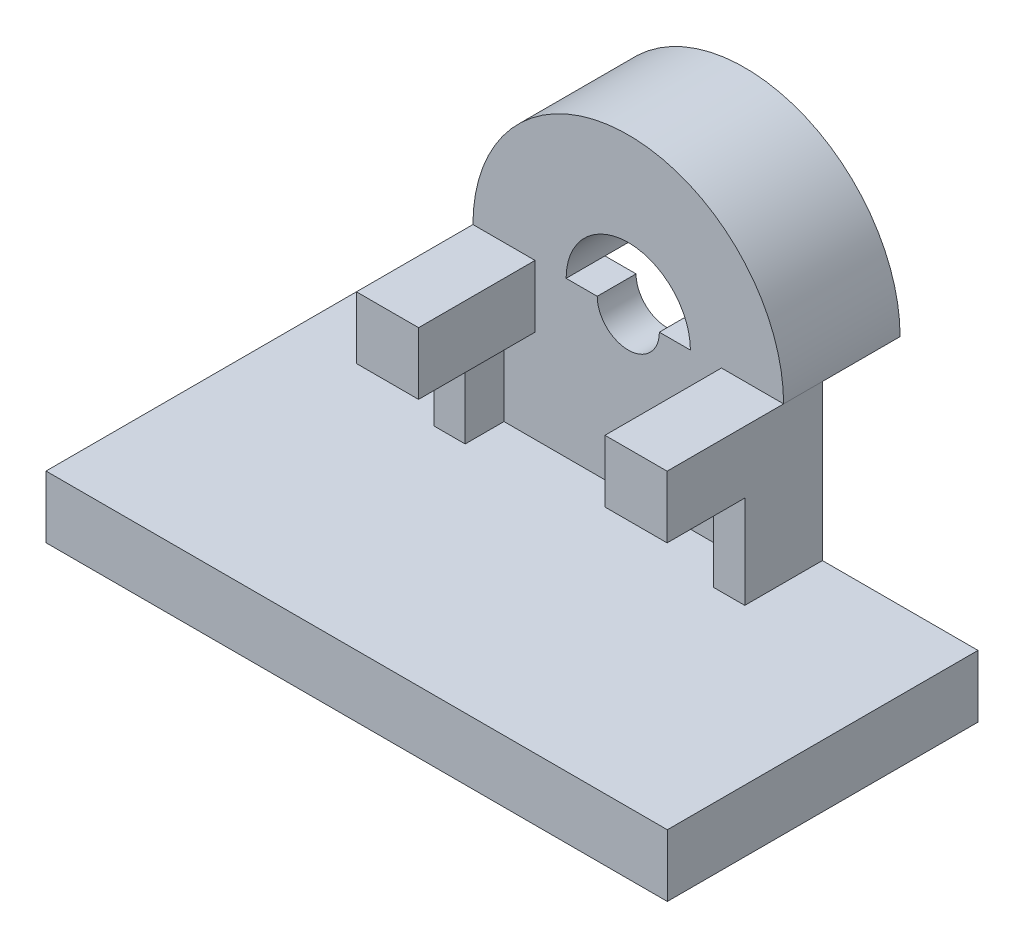
SolidWorks part; units mm, degrees
ref_plane "Front" through (0, 0, 0) normal (0, 0, 1) x (1, 0, 0)
ref_plane "Top" through (0, 0, 0) normal (0, 1, 0) x (1, 0, 0)
ref_plane "Right" through (0, 0, 0) normal (1, 0, 0) x (0, 0, -1)
sketch "Sketch1" plane through (0, 0, 0) normal (0, 0, 1) x (1, 0, 0)
  line L0 (-43.0941, -31.9264) -> (56.9059, -31.9264)
  line L1 (56.9059, -31.9264) -> (56.9059, -21.9264)
  line L2 (56.9059, -21.9264) -> (-43.0941, -21.9264)
  line L3 (-43.0941, -21.9264) -> (-43.0941, -31.9264)
  line L5 (-18.131, -21.9264) -> (-18.131, 3.0366)
  line L6 (-18.131, 3.0366) -> (31.869, 3.0366)
  line L7 (31.869, 3.0366) -> (31.869, -21.9264)
  line L10 (-8.131, 3.0366) -> (-8.131, -6.9634)
  line L11 (-8.131, -6.9634) -> (-18.131, -6.9634)
  line L13 (31.869, -6.9634) -> (21.869, -6.9634)
  line L14 (21.869, -6.9634) -> (21.869, 3.0366)
  line L15 (26.869, -6.9634) -> (26.869, -21.9264)
  line L16 (-13.131, -6.9634) -> (-13.131, -21.9264)
  arc A0 (31.869, 3.0366) -> (-18.131, 3.0366) centre (6.869, 3.0366) ccw
  arc A1 (16.869, 3.0366) -> (-3.131, 3.0366) centre (6.869, 3.0366) ccw
  arc A2 (1.869, 3.0366) -> (11.869, 3.0366) centre (6.869, 3.0366) ccw
extrude "Boss-Extrude1" add sketch "Sketch1" along normal blind 50 contours L2 L3 L0 L1 region at (6.9059, -26.9264, 0)
extrude "Boss-Extrude2" add sketch "Sketch1<6>" along normal blind 25 separate body contours L11 L10 L6 L5 | L14 L13 L7 L6 region at (-13.131, -1.9634, 0) region at (26.869, -1.9634, 0)
sketch "Sketch1<6>" plane through (0, 0, 0) normal (0, 0, 1) x (1, 0, 0) same geometry as "Sketch1"
extrude "Boss-Extrude3" add sketch "Sketch1<7>" along normal blind 12.5 contours L16 L11 L5 L2 | L13 L15 L2 L7 region at (-15.631, -14.4449, 0) region at (29.369, -14.4449, 0)
sketch "Sketch1<7>" plane through (0, 0, 0) normal (0, 0, 1) x (1, 0, 0) same geometry as "Sketch1"
extrude "Boss-Extrude4" add sketch "Sketch1<8>" along normal blind 6.25 contours A2 L6 L10 L11 L16 L2 L15 L13 L14 | A1 L6 A0 region at (6.869, -10.789, 0) region at (6.869, 14.8596, 0)
sketch "Sketch1<8>" plane through (0, 0, 0) normal (0, 0, 1) x (1, 0, 0) same geometry as "Sketch1"
extrude "Boss-Extrude5" add sketch "Sketch1<9>" against normal blind 12.5 contours A1 L6 A0 region at (6.869, 14.8596, 0)
sketch "Sketch1<9>" plane through (0, 0, 0) normal (0, 0, 1) x (1, 0, 0) same geometry as "Sketch1"
